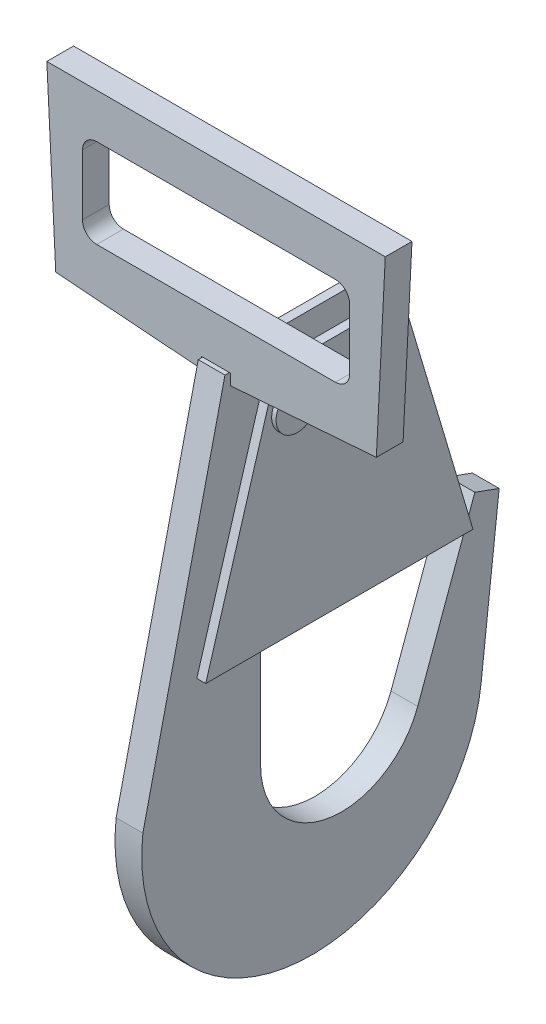
SolidWorks part; units mm, degrees
material "Alloy Steel"
ref_plane "Front Plane" through (0, 0, 0) normal (0, 0, 1) x (1, 0, 0)
ref_plane "Top Plane" through (0, 0, 0) normal (0, 1, 0) x (1, 0, 0)
ref_plane "Right Plane" through (0, 0, 0) normal (1, 0, 0) x (0, 0, -1)
sketch "Sketch1" plane through (0, 0, 0) normal (0, 0, 1) x (1, 0, 0)
  line L0 (30.1625, 19.05) -> (-30.1625, 19.05)
  line L1 (-30.1625, 19.05) -> (-28.575, -12.7)
  line L2 (-28.575, -12.7) -> (28.575, -12.7)
  line L3 (28.575, -12.7) -> (30.1625, 19.05)
  line L4 (0, -12.7) -> (0, 19.05) construction
  line L6 (23.8125, -4.7625) -> (-23.8125, -4.7625)
  line L7 (23.8125, -4.7625) -> (23.8125, 11.1125)
  line L8 (23.8125, 11.1125) -> (-23.8125, 11.1125)
  line L9 (-23.8125, -4.7625) -> (-23.8125, 11.1125)
  line L10 (23.8125, -4.7625) -> (-23.8125, 11.1125) construction
  line L11 (23.8125, 11.1125) -> (-23.8125, -4.7625) construction
  point P2 (0, 19.05)
  point P9 (0, 3.175)
  dimension "D1" = 60.325
  dimension "D2" = 31.75
  dimension "D3" = 15.875
  dimension "D4" = 47.625
  dimension "D5" = 57.15
extrude "Boss-Extrude1" add sketch "Sketch1" along normal mid plane 4.7625
sketch "Sketch2" plane through (0, 0, 0) normal (1, 0, 0) x (0, 0, -1)
  line L0 (-3.175, -12.7) -> (-17.8099, -76.0908)
  line L1 (3.175, -12.7) -> (3.175, -76.0908)
  line L2 (3.175, -76.0908) -> (31.1876, -81.0302) construction
  line L3 (-17.8099, -76.0908) -> (3.175, -76.0908) construction
  line L4 (-3.175, -12.7) -> (3.175, -12.7)
  line L5 (31.1876, -81.0302) -> (41.3667, -53.0635)
  line L6 (3.175, -76.0908) -> (-17.8099, -76.0908) construction
  line L7 (41.3667, -53.0635) -> (45.702, -54.6414)
  line L8 (45.702, -54.6414) -> (42.4957, -83.0241)
  line L9 (0, 33.1788) -> (0, -33.1788) construction
  line L10 (-2.3813, -12.7) -> (2.3813, -12.7) construction
  arc A0 (-17.8099, -76.0908) -> (42.4957, -83.0241) centre (12.336, -79.6169) ccw
  arc A1 (3.175, -76.0908) -> (31.1876, -81.0302) centre (17.6168, -76.0908) ccw
  point P12 (0, -12.7)
  dimension "D2" = 13
  dimension "D4" = 10
  dimension "D8" = 6.35
extrude "Boss-Extrude2" add sketch "Sketch2" along normal mid plane 4.7625
sketch "Sketch3" plane through (2.3813, 0, 0) normal (1, 0, 0) x (0, 0, -1)
  line L0 (37.8554, -57.0192) -> (-8.1903, -57.0192)
  line L2 (-8.1903, -57.0192) -> (4.349, -14.9738)
  line L3 (4.349, -14.9738) -> (25.3161, -14.9738)
  line L4 (25.3161, -14.9738) -> (37.8554, -57.0192)
  line L5 (14.8326, -14.9738) -> (14.8326, -57.0192) construction
extrude "Boss-Extrude3" add sketch "Sketch3" along normal blind 1.5875 separate body
mirror "Mirror1" about plane through (0, 0, 0) normal (1, 0, 0) of bodies 103
sketch "Sketch4" plane through (0, 5.7104, -19.1474) normal (0, 0.2858, -0.9583) x (-1, 0, 0)
  line L1 (-3.9688, -21.5844) -> (3.9687, -21.5844)
  line L2 (-3.9688, -21.5844) -> (-3.9687, -65.4598)
  line L3 (-3.9687, -65.4598) -> (3.9688, -65.4598)
  line L4 (3.9687, -21.5844) -> (3.9688, -65.4598)
extrude "Boss-Extrude4" add sketch "Sketch4" along direction (0, 0, 1) on the side of the normal blind 1.5875
sketch "Sketch5" plane through (0, 0, 0) normal (1, 0, 0) x (0, 0, -1)
  line L0 (3.175, -17.78) -> (12.065, -17.78)
  line L1 (3.175, -76.0908) -> (3.175, -12.7) construction
  line L2 (12.065, -17.78) -> (12.065, -26.67)
  line L3 (12.065, -26.67) -> (3.175, -26.67)
  line L4 (3.175, -17.78) -> (3.175, -26.67)
  dimension "D1" = 8.89
  dimension "D2" = 17.78
  dimension "D3" = 8.89
extrude "Boss-Extrude5" add sketch "Sketch5" along normal mid plane 4.7625
fillet "Fillet4" radius 2.54 4 edges at (0, -17.78, -12.065) (0, -26.67, -12.065) (0, -26.67, -3.175) (0, -17.78, -3.175)
sketch "Sketch6" plane through (3.9688, 0, 0) normal (1, 0, 0) x (0, 0, -1)
  circle A0 centre (7.3701, -21.8315) radius 3.81
  dimension "D1" = 7.62
extrude "Boss-Extrude6" add sketch "Sketch6" along normal blind 0.7937 separate body
mirror "Mirror2" about plane through (0, 0, 0) normal (1, 0, 0) of bodies 107
sketch "Sketch7" plane through (0, 0, -2.3813) normal (0, 0, -1) x (-1, 0, 0)
  line L0 (-28.575, -12.7) -> (-2.5888, -14.6466)
  line L1 (-2.5888, -14.6466) -> (-2.5888, -12.7)
  line L2 (-2.3813, -12.7) -> (-28.575, -12.7) construction
  line L3 (-2.5888, -12.7) -> (-28.575, -12.7)
extrude "Boss-Extrude7" add sketch "Sketch7" along direction (0, 0, 1) on the side against the normal up to surface (4.7625 mm away) separate body up to face at (0, -2.1167, 2.3813)
mirror "Mirror3" about plane through (0, 0, 0) normal (1, 0, 0) of bodies 109
combine bodies "Combine1" operation type add bodies to combine 109 106 110
fillet "Fillet5" radius 2.54 4 edges at (23.8125, -4.7625, 0) (23.8125, 11.1125, 0) (-23.8125, 11.1125, 0) (-23.8125, -4.7625, 0)
